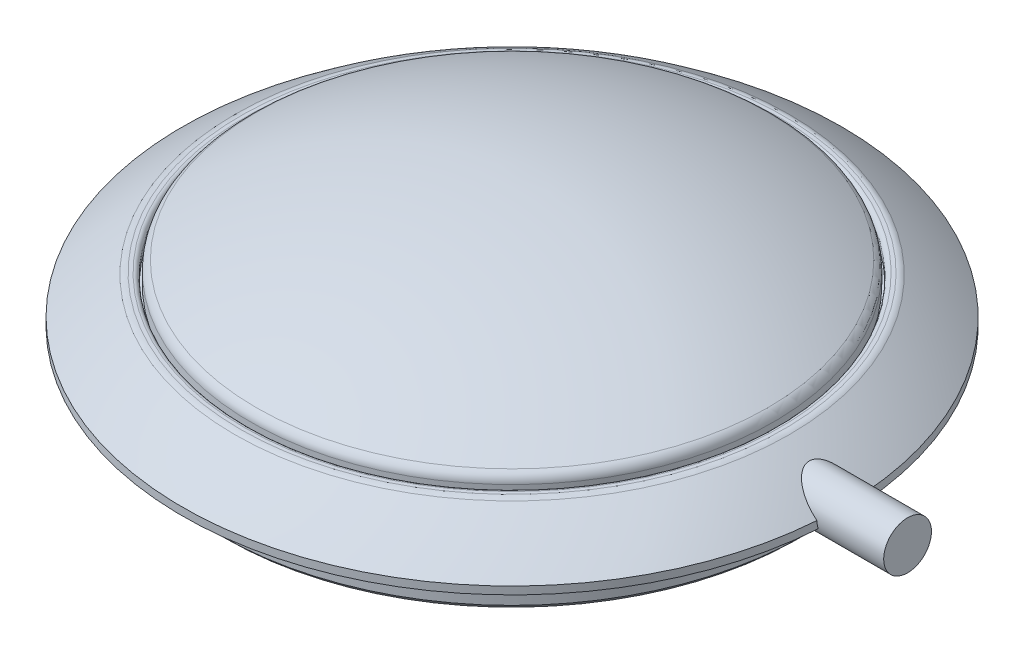
SolidWorks part; units mm, degrees
material "ABS"
ref_plane "Front" through (0, 0, 0) normal (0, 0, 1) x (1, 0, 0)
ref_plane "Top" through (0, 0, 0) normal (0, 1, 0) x (1, 0, 0)
ref_plane "Right" through (0, 0, 0) normal (1, 0, 0) x (0, 0, -1)
sketch "Эскиз1" plane through (0, 0, 0) normal (0, 1, 0) x (1, 0, 0)
  circle A0 centre (0, 0) radius 30
  dimension "D1" = 60
extrude "Бобышка-Вытянуть1" add sketch "Эскиз1" along normal blind 15
sketch "Эскиз2" plane through (0, 0, 0) normal (0, 1, 0) x (1, 0, 0)
  circle A0 centre (0, 0) radius 26.5
  circle A1 centre (0, 0) radius 27.5
  dimension "D1" = 55
  dimension "D2" = 53
extrude "Вырез-Вытянуть1" cut sketch "Эскиз2" along normal blind 3.8 flip side to cut contours A1
extrude "Вырез-Вытянуть2" cut sketch "Эскиз2<3>" along normal blind 3.3 flip side to cut contours A0
sketch "Эскиз2<3>" plane through (0, 0, 0) normal (0, 1, 0) x (1, 0, 0) same geometry as "Эскиз2"
sketch "Эскиз3" plane through (0, 0, 0) normal (0, 0, 1) x (1, 0, 0)
  line L0 (0, 0) -> (0, 4.5) construction
  line L1 (-26.5, 0) -> (26.5, 0) construction
  line L2 (0, 4.5) -> (-30, 4.5) construction
  line L3 (0, 0) -> (0, 15) construction
  line L4 (0, 4.5) -> (30, 4.5) construction
  line L5 (-30, 4.5) -> (-42.195, 4.5)
  line L6 (-42.195, 4.5) -> (-42.195, 24.0715)
  line L7 (-42.195, 24.0715) -> (0, 24.0715)
  line L8 (0, 24.0715) -> (0, 15)
  line L9 (-25, -1.5441) -> (-25, 7.9939) construction
  line L10 (-25, 7.9939) -> (-24, 7.9939)
  line L11 (-24, 7.9939) -> (-24, 6.9939)
  line L12 (-24, 6.9939) -> (-23.8, 6.9939)
  line L13 (-23.8, 6.9939) -> (-23.8, 8.7002)
  arc A0 (-30, 4.5) -> (30, 4.5) centre (0, -33.1071) cw
  dimension "D1" = 4.5
  dimension "D2" = 15
  dimension "D3" = 30
  dimension "D4" = 30
  dimension "D5" = 5
  dimension "D6" = 1
  dimension "D7" = 0.2
  dimension "D8" = 1
revolve "Вырез-Повернуть1" cut sketch "Эскиз3" angle 360 about L3 region at (-24.5002, 16.2378, 0) region at (-24.106, 7.9962, 0)
sketch "Эскиз4" plane through (0, 0, 0) normal (1, 0, 0) x (0, 0, -1)
  line L0 (0, 0) -> (0, 4.5)
  circle A0 centre (0, 4.5) radius 2.175
  dimension "D2" = 4.35
  dimension "D1" = 4.5
extrude "Бобышка-Вытянуть2" add sketch "Эскиз4" along normal blind 36 contours A0 region at (0, 3.0055, -1.4945)
chamfer "Фаска1" distance 0.5 angle 45 1 edges at (0, 0, 26.5)
fillet "Скругление1" radius 1 2 edges at (0, 8.7002, -23.8) (0, 7.9939, -25)
fillet "Скругление2" radius 0.4 1 edges at (0, 7.9939, -24)
